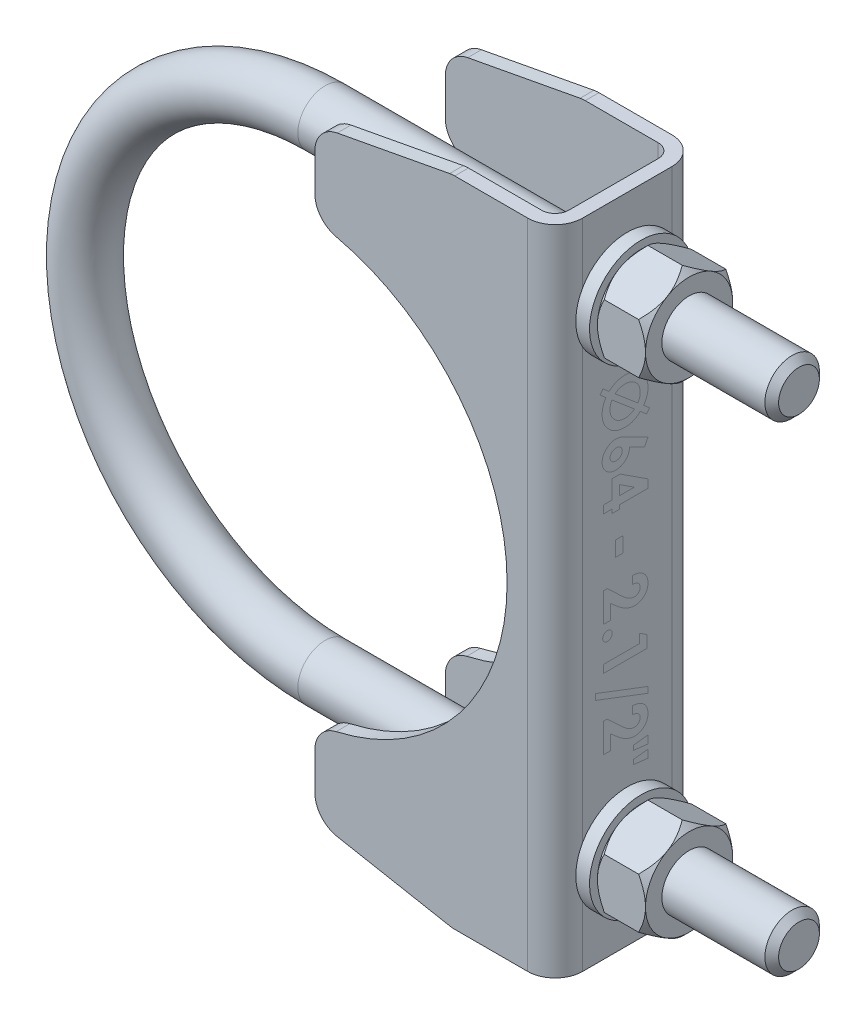
SolidWorks part; units mm, degrees
material "SAE 1045"
ref_plane "Front Plane" through (0, 0, 0) normal (0, 0, 1) x (1, 0, 0)
ref_plane "Top Plane" through (0, 0, 0) normal (0, 1, 0) x (1, 0, 0)
ref_plane "Right Plane" through (0, 0, 0) normal (1, 0, 0) x (0, 0, -1)
sketch "Esboço1" plane through (0, 0, 0) normal (0, 0, 1) x (1, 0, 0)
  line L0 (-69, 65.9687) -> (0, 65.9687) construction
  line L1 (-69, 3.9688) -> (0, 3.9688) construction
  line L2 (-69, 0) -> (0, 0)
  line L3 (-69, 69.9375) -> (0, 69.9375)
  line L4 (0, 69.9375) -> (0, 65.9687) construction
  line L5 (0, 0) -> (0, 3.9688) construction
  arc A0 (-69, 65.9687) -> (-69, 3.9688) centre (-69, 34.9688) ccw construction
  arc A1 (-69, 69.9375) -> (-69, 0) centre (-69, 34.9688) ccw
  arc A2 (-69, 65.9687) -> (-69, 3.9688) centre (-69, 34.9688) ccw construction
  dimension "D2" = 31
  dimension "D3" = 100
  dimension "D1" = 3.9688
sketch "Esboço2" plane through (0, 0, 0) normal (1, 0, 0) x (0, 0, -1)
  circle A0 centre (0, 0) radius 3.9688
sweep "Varredura1" add profiles "Esboço2" path "Esboço1"
cosmetic thread "Representação de rosca1" parameters "D1"=25, "D2"=6.2586
cosmetic thread "Representação de rosca2" parameters "D1"=25, "D2"=6.2586
chamfer "Chanfro1" distance 1 angle 45 2 edges at (0, 0, -3.9688) (0, 69.9375, -3.9688)
ref_plane "Plano1" through (-25, 0, 0) normal (1, 0, 0) x (0, 0, -1)
sketch "Esboço3" plane through (-25, 0, 0) normal (1, 0, 0) x (0, 0, -1)
  line L0 (0, 0) -> (0, 69.9375) construction
  line L1 (10.5, 82.4688) -> (-10.5, 82.4688)
  line L2 (10.5, 82.4688) -> (10.5, -12.5313)
  line L3 (10.5, -12.5313) -> (-10.5, -12.5313)
  line L4 (-10.5, 82.4688) -> (-10.5, -12.5313)
  line L5 (10.5, 82.4688) -> (-10.5, -12.5313) construction
  line L6 (10.5, -12.5313) -> (-10.5, 82.4688) construction
  line L7 (0, 71.6875) -> (0, 68.1875) construction
  line L8 (4.25, 71.6875) -> (4.25, 68.1875)
  line L9 (-4.25, 71.6875) -> (-4.25, 68.1875)
  line L10 (0, -1.75) -> (0, 1.75) construction
  line L11 (-4.25, -1.75) -> (-4.25, 1.75)
  line L12 (4.25, -1.75) -> (4.25, 1.75)
  arc A0 (4.25, 71.6875) -> (-4.25, 71.6875) centre (0, 71.6875) ccw
  arc A1 (-4.25, 68.1875) -> (4.25, 68.1875) centre (0, 68.1875) ccw
  arc A2 (-4.25, -1.75) -> (4.25, -1.75) centre (0, -1.75) ccw
  arc A3 (4.25, 1.75) -> (-4.25, 1.75) centre (0, 1.75) ccw
  point P0 (0, 34.9687)
  point P11 (0, 69.9375)
  point P17 (0, 0)
  dimension "D4" = 12
  dimension "D1" = 95
  dimension "D2" = 21
  dimension "D3" = 8.5
extrude "Ressalto-extrusão1" add sketch "Esboço3" against normal blind 2 separate body
sketch "Esboço4" plane through (0, 0, 10.5) normal (0, 0, 1) x (1, 0, 0)
  line L0 (-27, 82.4688) -> (-27, -12.5313) construction
  line L1 (-27, 82.4688) -> (-27, -12.5313)
  line L2 (-27, 82.4688) -> (-40, 82.4688)
  line L3 (-40, 82.4688) -> (-60, 78.7178)
  line L4 (-60, 78.7178) -> (-60, 66.7178)
  line L5 (-60, 3.2197) -> (-60, -8.7803)
  line L6 (-60, -8.7803) -> (-40, -12.5313)
  line L7 (-40, -12.5313) -> (-27, -12.5313)
  line L8 (-25, 82.4688) -> (-25, -12.5313) construction
  arc A0 (-60, 66.7178) -> (-60, 3.2197) centre (-64, 34.9687) cw
  dimension "D1" = 35
  dimension "D4" = 7
  dimension "D5" = 12
  dimension "D3" = 32
  dimension "D2" = 15
extrude "Ressalto-extrusão2" add sketch "Esboço4" against normal blind 2
mirror "Espelhar1" about plane through (0, 0, 0) normal (0, 0, 1) of "Ressalto-extrusão2"
fillet "Filete1" radius 2 2 edges at (-27, 34.9687, -8.5)
fillet "Filete2" radius 4 12 edges at (-60, 66.7178, -9.5) (-60, 78.7178, -9.5) (-60, 3.2197, -9.5) (-60, -8.7803, -9.5) (-60, -8.7803, 9.5) (-60, 3.2197, 9.5) (-60, 66.7178, 9.5) (-60, 78.7178, 9.5) (-40, 82.4688, 9.5) (-40, 82.4688, -9.5) (-25, 34.9687, -10.5) (-25, 34.9687, 10.5)
sketch "Esboço5" plane through (-25, 0, 0) normal (1, 0, 0) x (0, 0, -1)
  circle A0 centre (0, 69.9375) radius 7.5
  circle A1 centre (0, 0) radius 7.5
  circle A2 centre (0, 69.9375) radius 5
  circle A3 centre (0, 0) radius 5
  dimension "D1" = 15
  dimension "D2" = 10
extrude "Ressalto-extrusão3" add sketch "Esboço5" along normal blind 2
sketch "Esboço6" plane through (-23, 0, 0) normal (1, 0, 0) x (0, 0, -1)
  line L1 (-6.35, 73.6037) -> (-6.35, 66.2713)
  line L2 (-6.35, 66.2713) -> (0, 62.6052)
  line L3 (0, 62.6052) -> (6.35, 66.2713)
  line L4 (6.35, 66.2713) -> (6.35, 73.6037)
  line L5 (6.35, 73.6037) -> (0, 77.2698)
  line L6 (0, 77.2698) -> (-6.35, 73.6037)
  line L7 (6.35, 3.6662) -> (0, 7.3323)
  line L8 (0, 7.3323) -> (-6.35, 3.6662)
  line L9 (-6.35, 3.6662) -> (-6.35, -3.6662)
  line L10 (-6.35, -3.6662) -> (0, -7.3323)
  line L11 (0, -7.3323) -> (6.35, -3.6662)
  line L12 (6.35, -3.6662) -> (6.35, 3.6662)
  circle A0 centre (0, 69.9375) radius 6.35 construction
  circle A1 centre (0, 0) radius 6.35 construction
  dimension "D1" = 12.7
extrude "Ressalto-extrusão4" add sketch "Esboço6" along normal blind 7
sketch "Esboço7" plane through (0, 0, 0) normal (0, 0, 1) x (1, 0, 0)
  line L0 (-16, 76.2875) -> (-16, 77.2698)
  line L1 (-16, 77.2698) -> (-16, 73.6037) construction
  line L2 (-16, 77.2698) -> (-17, 77.2698)
  line L3 (-16, 77.2698) -> (-23, 77.2698) construction
  line L4 (-17, 77.2698) -> (-16, 76.2875)
  line L5 (0, 69.9375) -> (-31.8387, 69.9375) construction
  line L6 (0, 66.9687) -> (0, 72.9062) construction
  line L7 (-19.5, 77.2698) -> (-19.5, 85.6682) construction
  line L8 (-23, 76.2875) -> (-23, 77.2698)
  line L9 (-23, 77.2698) -> (-22, 77.2698)
  line L10 (-22, 77.2698) -> (-23, 76.2875)
  dimension "D1" = 12.7
  dimension "D2" = 1
revolve "Corte-Revolução1" cut sketch "Esboço7" angle 360 about L5
sketch "Esboço8" plane through (0, 0, 0) normal (0, 0, 1) x (1, 0, 0)
  line L0 (-16, 7.3323) -> (-17, 7.3323)
  line L1 (-16, 7.3323) -> (-23, 7.3323) construction
  line L2 (-17, 7.3323) -> (-16, 6.35)
  line L3 (-16, 7.3323) -> (-16, 3.6662) construction
  line L4 (-16, 6.35) -> (-16, 7.3323)
  line L5 (0, 0) -> (-19.7084, 0) construction
  line L6 (0, -2.9687) -> (0, 2.9687) construction
  line L7 (-19.5, 7.3323) -> (-19.5, 11.7477) construction
  line L8 (-23, 6.35) -> (-23, 7.3323)
  line L9 (-23, 7.3323) -> (-22, 7.3323)
  line L10 (-22, 7.3323) -> (-23, 6.35)
  dimension "D1" = 12.7
  dimension "D2" = 1
revolve "Corte-Revolução2" cut sketch "Esboço8" angle 360 about L5
sketch "Esboço9" plane through (-25, 0, 0) normal (1, 0, 0) x (0, 0, -1)
  line L0 (-3.5, 63.3043) -> (-3.5, 6.6332) construction
  line L1 (-10.5, -12.5313) -> (-10.5, 82.4688) construction
  arc A0 (6.5, 3.7417) -> (-6.5, 3.7417) centre (0, 0) ccw construction
  arc A1 (-6.5, 66.1958) -> (6.5, 66.1958) centre (0, 69.9375) ccw construction
  text T0 "Ø64 - 2.1/2\"" font "Century Gothic" height in points 24
  dimension "D1" = 7
wrap "Envolver1" sketch "Esboço9" wrap type scribe source sketch "Esboço9" face at (-25, 34.9687, 0)
